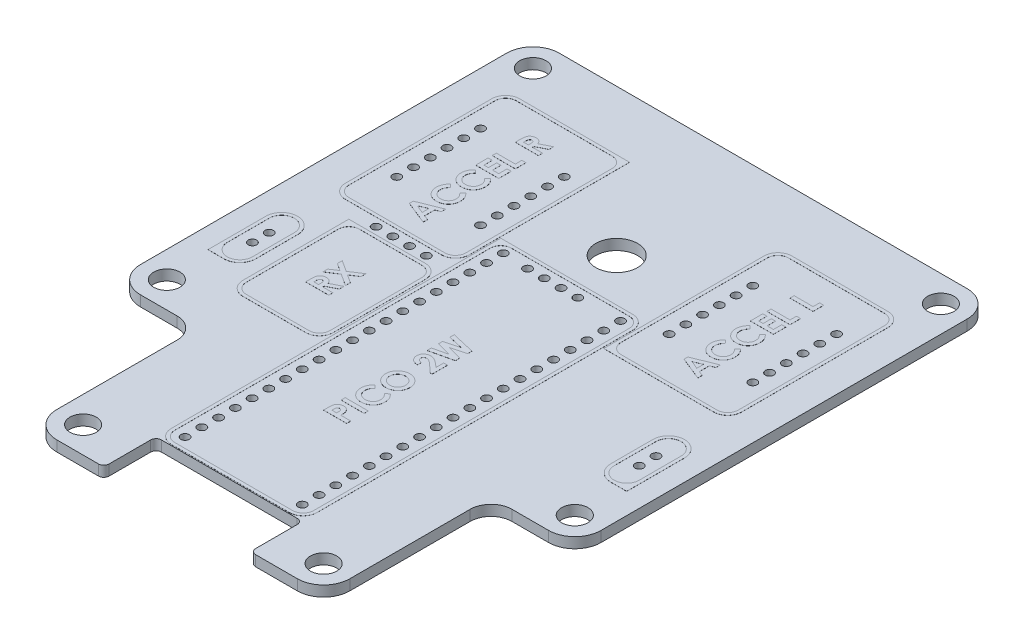
SolidWorks part; units mm, degrees
ref_plane "Front Plane" through (0, 0, 0) normal (0, 0, 1) x (1, 0, 0)
ref_plane "Top Plane" through (0, 0, 0) normal (0, 1, 0) x (1, 0, 0)
ref_plane "Right Plane" through (0, 0, 0) normal (1, 0, 0) x (0, 0, -1)
sketch "Sketch1" plane through (0, 0, 0) normal (0, 1, 0) x (1, 0, 0)
  line L0 (-22.225, -31.75) -> (-22.225, -57.15)
  line L1 (-34.925, -31.75) -> (-22.225, -31.75)
  line L2 (-34.925, -31.75) -> (-34.925, 31.75)
  line L3 (-34.925, 31.75) -> (34.925, 31.75)
  line L4 (34.925, -31.75) -> (34.925, 31.75)
  line L5 (-34.925, -31.75) -> (34.925, 31.75) construction
  line L6 (-34.925, 31.75) -> (34.925, -31.75) construction
  line L7 (-22.225, -57.15) -> (22.225, -57.15)
  line L8 (22.225, -57.15) -> (22.225, -31.75)
  line L9 (22.225, -31.75) -> (34.925, -31.75)
  point P0 (0, 0)
  point P9 (0, -57.15)
  dimension "D1" = 69.85
  dimension "D2" = 63.5
  dimension "D3" = 44.45
  dimension "D4" = 25.4
extrude "Boss-Extrude1" add sketch "Sketch1" along normal blind 1.6002
sketch "Sketch2" plane through (0, 1.6002, 0) normal (0, 1, 0) x (1, 0, 0)
  line L1 (-10.541, -48.5648) -> (10.541, -48.5648) construction
  line L2 (-10.541, -48.5648) -> (-10.541, 2.4892) construction
  line L3 (-10.541, 2.4892) -> (10.541, 2.4892) construction
  line L4 (10.541, -48.5648) -> (10.541, 2.4892) construction
  line L5 (-10.541, -48.5648) -> (10.541, 2.4892) construction
  line L6 (-10.541, 2.4892) -> (10.541, -48.5648) construction
  line L7 (-8.89, 1.2192) -> (8.89, 1.2192) construction
  circle A0 centre (-8.89, 1.2192) radius 0.635
  circle A1 centre (8.89, 1.2192) radius 0.635
  point P0 (0, -23.0378)
  point P7 (0, 1.2192)
  dimension "D5" = 1.27
  dimension "D1" = 21.082
  dimension "D2" = 51.054
  dimension "D3" = 23.0378
  dimension "D4" = 8.89
  dimension "D6" = 1.27
extrude "Cut-Extrude1" cut sketch "Sketch2" against normal blind 1.6002
pattern_linear "LPattern1" count 20 spacing 2.54 along (0, 0, 1) of "Cut-Extrude1"
sketch "Sketch3" plane through (0, 1.6002, 0) normal (0, 1, 0) x (1, 0, 0)
  line L0 (-27.0002, 15.875) -> (-14.3002, 15.875) construction
  line L1 (-29.5402, -3.175) -> (-11.7602, -3.175) construction
  line L2 (-29.5402, -3.175) -> (-29.5402, 22.225) construction
  line L3 (-29.5402, 22.225) -> (-11.7602, 22.225) construction
  line L4 (-11.7602, -3.175) -> (-11.7602, 22.225) construction
  line L5 (-29.5402, -3.175) -> (-11.7602, 22.225) construction
  line L6 (-29.5402, 22.225) -> (-11.7602, -3.175) construction
  line L7 (-20.6502, 15.875) -> (-20.6502, 9.525) construction
  line L9 (14.3002, 15.875) -> (27.0002, 15.875) construction
  line L10 (11.7602, -3.175) -> (29.5402, -3.175) construction
  line L11 (11.7602, -3.175) -> (11.7602, 22.225) construction
  line L12 (11.7602, 22.225) -> (29.5402, 22.225) construction
  line L13 (29.5402, -3.175) -> (29.5402, 22.225) construction
  line L14 (11.7602, -3.175) -> (29.5402, 22.225) construction
  line L15 (11.7602, 22.225) -> (29.5402, -3.175) construction
  line L16 (20.6502, 15.875) -> (20.6502, 9.525) construction
  line L17 (-11.7602, 22.225) -> (11.7602, 22.225) construction
  line L18 (0, 0) -> (0, 22.225) construction
  circle A0 centre (-14.3002, 15.875) radius 0.635
  circle A1 centre (-27.0002, 15.875) radius 0.635
  circle A2 centre (-8.89, 1.2192) radius 0.635 construction
  circle A3 centre (27.0002, 15.875) radius 0.635
  circle A4 centre (14.3002, 15.875) radius 0.635
  point P0 (-20.6502, 9.525)
  point P16 (20.6502, 9.525)
  dimension "D1" = 17.78
  dimension "D2" = 25.4
  dimension "D3" = 12.7
  dimension "D4" = 6.35
  dimension "D5" = 9.525
  dimension "D6" = 20.6502
  dimension "D7" = 17.78
  dimension "D8" = 25.4
extrude "Cut-Extrude2" cut sketch "Sketch3" against normal through all both and the other way through all
pattern_linear "LPattern2" count 6 spacing 2.54 along (0, 0, 1) of "Cut-Extrude2"
fillet "Fillet1" radius 3.9878 6 edges at (-34.925, 0.8001, -31.75) (34.925, 0.8001, -31.75) (-34.925, 0.8001, 31.75) (-22.225, 0.8001, 57.15) (22.225, 0.8001, 57.15) (34.925, 0.8001, 31.75)
sketch "Sketch9" plane through (0, 1.6002, 0) normal (0, 1, 0) x (1, 0, 0)
  line L1 (-30.9372, -27.7622) -> (30.9372, -27.7622) construction
  line L2 (-30.9372, -27.7622) -> (-30.9372, 27.7622) construction
  line L3 (-30.9372, 27.7622) -> (30.9372, 27.7622) construction
  line L4 (30.9372, -27.7622) -> (30.9372, 27.7622) construction
  line L5 (-30.9372, -27.7622) -> (30.9372, 27.7622) construction
  line L6 (-30.9372, 27.7622) -> (30.9372, -27.7622) construction
  circle A0 centre (-30.9372, 27.7622) radius 1.9939
  circle A1 centre (30.9372, 27.7622) radius 1.9939
  circle A2 centre (30.9372, -27.7622) radius 1.9939
  circle A3 centre (-30.9372, -27.7622) radius 1.9939
  arc A4 (-30.9372, 31.75) -> (-34.925, 27.7622) centre (-30.9372, 27.7622) ccw construction
  circle A5 centre (-18.2372, -53.1622) radius 1.9939
  circle A6 centre (18.2372, -53.1622) radius 1.9939
  point P0 (0, 0)
  dimension "D1" = 3.9878
extrude "Cut-Extrude4" cut sketch "Sketch9" against normal through all both and the other way through all
fillet "Fillet3" radius 3.175 2 edges at (22.225, 0.8001, 31.75) (-22.225, 0.8001, 31.75)
sketch "Sketch13" plane through (0, 1.6002, 0) normal (0, 1, 0) x (1, 0, 0)
  line L0 (-10.541, 0.889) -> (-10.541, -46.9646)
  line L1 (-8.9408, -48.5648) -> (8.9408, -48.5648)
  line L2 (10.541, -46.9646) -> (10.541, 0.889)
  line L3 (8.9408, 2.4892) -> (-8.9408, 2.4892)
  line L5 (-8.9408, -49.0728) -> (8.9408, -49.0728)
  line L6 (11.049, -46.9646) -> (11.049, 0.889)
  line L13 (-29.5402, 20.6248) -> (-29.5402, -1.5748)
  line L14 (-27.94, -3.175) -> (-13.3604, -3.175)
  line L15 (-11.7602, -1.5748) -> (-11.7602, 20.6248)
  line L16 (-13.3604, 22.225) -> (-27.94, 22.225)
  line L17 (11.7602, 20.6248) -> (11.7602, -1.5748)
  line L18 (13.3604, -3.175) -> (27.94, -3.175)
  line L19 (29.5402, -1.5748) -> (29.5402, 20.6248)
  line L20 (27.94, 22.225) -> (13.3604, 22.225)
  line L22 (-30.0482, 20.6248) -> (-30.0482, -1.5748)
  line L23 (-27.94, -3.683) -> (-13.3604, -3.683)
  line L25 (27.94, 22.733) -> (13.3604, 22.733)
  line L28 (30.0482, -1.5748) -> (30.0482, 20.6248)
  line L29 (-11.049, 0.889) -> (-11.049, -46.9646) construction
  line L30 (8.9408, 2.9972) -> (-8.9408, 2.9972) construction
  line L31 (8.9408, 2.9972) -> (-11.049, 2.9972)
  line L32 (-11.049, -46.9646) -> (-11.049, 2.9972)
  line L57 (-11.2522, -1.5748) -> (-11.2522, 20.6248) construction
  line L58 (-13.3604, 22.733) -> (-27.94, 22.733) construction
  line L59 (-27.94, 22.733) -> (-11.2522, 22.733)
  line L60 (-11.2522, 22.733) -> (-11.2522, -1.5748)
  line L61 (13.3604, -3.683) -> (27.94, -3.683) construction
  line L62 (11.2522, 20.6248) -> (11.2522, -1.5748) construction
  line L63 (11.2522, 20.6248) -> (11.2522, -3.683)
  line L64 (11.2522, -3.683) -> (27.94, -3.683)
  arc A0 (8.9408, 2.4892) -> (10.541, 0.889) centre (8.9408, 0.889) cw
  arc A1 (10.541, -46.9646) -> (8.9408, -48.5648) centre (8.9408, -46.9646) cw
  arc A2 (-8.9408, -48.5648) -> (-10.541, -46.9646) centre (-8.9408, -46.9646) cw
  arc A3 (-10.541, 0.889) -> (-8.9408, 2.4892) centre (-8.9408, 0.889) cw
  arc A4 (-8.9408, -49.0728) -> (-11.049, -46.9646) centre (-8.9408, -46.9646) cw
  arc A5 (11.049, -46.9646) -> (8.9408, -49.0728) centre (8.9408, -46.9646) cw
  arc A6 (8.9408, 2.9972) -> (11.049, 0.889) centre (8.9408, 0.889) cw
  arc A9 (11.7602, -1.5748) -> (13.3604, -3.175) centre (13.3604, -1.5748) ccw
  arc A10 (27.94, -3.175) -> (29.5402, -1.5748) centre (27.94, -1.5748) ccw
  arc A11 (29.5402, 20.6248) -> (27.94, 22.225) centre (27.94, 20.6248) ccw
  arc A12 (13.3604, 22.225) -> (11.7602, 20.6248) centre (13.3604, 20.6248) ccw
  arc A13 (-13.3604, 22.225) -> (-11.7602, 20.6248) centre (-13.3604, 20.6248) cw
  arc A14 (-11.7602, -1.5748) -> (-13.3604, -3.175) centre (-13.3604, -1.5748) cw
  arc A15 (-27.94, -3.175) -> (-29.5402, -1.5748) centre (-27.94, -1.5748) cw
  arc A16 (-29.5402, 20.6248) -> (-27.94, 22.225) centre (-27.94, 20.6248) cw
  arc A17 (-30.0482, 20.6248) -> (-27.94, 22.733) centre (-27.94, 20.6248) cw
  arc A18 (-27.94, -3.683) -> (-30.0482, -1.5748) centre (-27.94, -1.5748) cw
  arc A19 (-11.2522, -1.5748) -> (-13.3604, -3.683) centre (-13.3604, -1.5748) cw
  arc A21 (13.3604, 22.733) -> (11.2522, 20.6248) centre (13.3604, 20.6248) ccw
  arc A23 (27.94, -3.683) -> (30.0482, -1.5748) centre (27.94, -1.5748) ccw
  arc A24 (30.0482, 20.6248) -> (27.94, 22.733) centre (27.94, 20.6248) ccw
  arc A25 (-11.049, 0.889) -> (-8.9408, 2.9972) centre (-8.9408, 0.889) cw construction
  arc A43 (-13.3604, 22.733) -> (-11.2522, 20.6248) centre (-13.3604, 20.6248) cw construction
  arc A44 (11.2522, -1.5748) -> (13.3604, -3.683) centre (13.3604, -1.5748) ccw construction
  point P10 (10.541, 2.4892)
  point P13 (10.541, -48.5648)
  point P16 (-10.541, -48.5648)
  point P19 (-10.541, 2.4892)
  point P53 (11.7602, -3.175)
  point P56 (29.5402, -3.175)
  point P59 (29.5402, 22.225)
  point P62 (11.7602, 22.225)
  point P68 (-11.7602, -3.175)
  point P71 (-29.5402, -3.175)
  point P74 (-29.5402, 22.225)
  point P153 (26.5939, -10.8077)
  point P154 (0, 0)
  dimension "D1" = 1.6002
  dimension "D4" = 1.6002
  dimension "D13" = 0.508
  dimension "D2" = 0.508
  dimension "D5" = 0.508
extrude "Boss-Extrude5" add sketch "Sketch13" along normal blind 0.0127 contours A19 L60 L59 A17 L22 A18 L23 L13 A16 L16 A13 L15 A14 L14 A15 | L28 A24 L25 A21 L63 L64 A23 A12 L20 A11 L19 A10 L18 A9 L17 | A6 L31 L32 A4 L5 A5 L6 L0 A3 L3 A0 L2 A1 L1 A2 region at (-10.3915, 1.6002, 48.4153) region at (-29.2015, 1.6002, -21.8863) region at (29.2015, 1.6002, -21.8863)
sketch "Sketch15" plane through (0, 0, 0) normal (0, -1, 0) x (1, 0, 0)
  line L0 (-5.334, 1.3766) -> (2.8956, 1.3766)
  line L1 (-5.334, -2.9414) -> (2.8956, -2.9414)
  line L2 (-6.9342, -1.3412) -> (-6.9342, -0.7316)
  line L3 (-5.334, 0.8686) -> (2.8956, 0.8686)
  line L4 (4.4958, -1.3412) -> (4.4958, -0.7316)
  line L5 (-6.9342, -2.9414) -> (4.4958, 0.8686) construction
  line L6 (-6.9342, 0.8686) -> (4.4958, -2.9414) construction
  line L7 (5.0038, -1.3412) -> (5.0038, -0.7316)
  line L8 (-5.334, -3.4494) -> (2.8956, -3.4494)
  line L9 (-7.4422, -1.3412) -> (-7.4422, -0.7316)
  line L10 (2.8956, 1.3766) -> (5.0038, 1.3766)
  line L11 (5.0038, 1.3766) -> (5.0038, -0.7316)
  arc A0 (-5.334, 0.8686) -> (-6.9342, -0.7316) centre (-5.334, -0.7316) ccw
  arc A1 (-6.9342, -1.3412) -> (-5.334, -2.9414) centre (-5.334, -1.3412) ccw
  arc A2 (2.8956, -2.9414) -> (4.4958, -1.3412) centre (2.8956, -1.3412) ccw
  arc A3 (4.4958, -0.7316) -> (2.8956, 0.8686) centre (2.8956, -0.7316) ccw
  arc A4 (5.0038, -0.7316) -> (2.8956, 1.3766) centre (2.8956, -0.7316) ccw construction
  arc A5 (2.8956, -3.4494) -> (5.0038, -1.3412) centre (2.8956, -1.3412) ccw
  arc A6 (-7.4422, -1.3412) -> (-5.334, -3.4494) centre (-5.334, -1.3412) ccw
  arc A7 (-5.334, 1.3766) -> (-7.4422, -0.7316) centre (-5.334, -0.7316) ccw
  point P0 (-1.2192, -1.0364)
  point P32 (-1.2192, -2.9414)
  dimension "D1" = 1.6002
  dimension "D2" = 11.43
  dimension "D3" = 3.81
  dimension "D5" = 1.6002
  dimension "D6" = 1.2192
  dimension "D4" = 0.508
sketch "Sketch16" plane through (0, 1.6002, 0) normal (0, 1, 0) x (1, 0, 0)
  line L0 (-11.1125, -57.15) -> (-11.1125, -50.038)
  line L1 (-18.2372, -57.15) -> (18.2372, -57.15) construction
  line L2 (-10.2997, -49.2252) -> (10.2997, -49.2252)
  line L3 (11.1125, -50.038) -> (11.1125, -57.15)
  line L4 (11.1125, -57.15) -> (-11.1125, -57.15)
  arc A0 (11.1125, -50.038) -> (10.2997, -49.2252) centre (10.2997, -50.038) ccw
  arc A1 (-11.1125, -50.038) -> (-10.2997, -49.2252) centre (-10.2997, -50.038) cw
  point P8 (11.1125, -49.2252)
  point P11 (-11.1125, -49.2252)
  point P12 (0, -49.2252)
  point P13 (0, 0)
  dimension "D3" = 0.8128
  dimension "D1" = 22.225
  dimension "D2" = 7.9248
extrude "Cut-Extrude12" cut sketch "Sketch16" against normal through all both and the other way through all
fillet "Fillet4" radius 0.8128 2 edges at (11.1125, 0.8001, 57.15) (-11.1125, 0.8001, 57.15)
sketch "Sketch11" plane through (0, 1.6002, 0) normal (0, 1, 0) x (1, 0, 0)
  line L0 (0, 0) -> (0, 22.225) construction
  circle A0 centre (0, 9.525) radius 3.175
  dimension "D1" = 6.35
extrude "Cut-Extrude6" cut sketch "Sketch11" against normal through all both and the other way through all
sketch "Sketch18" plane through (0, 1.6002, 0) normal (0, 1, 0) x (1, 0, 0)
  line L0 (-22.0218, -4.9403) -> (-19.4818, -4.9403) construction
  line L1 (-24.5618, -6.5405) -> (-11.8618, -6.5405) construction
  line L2 (-24.5618, -6.5405) -> (-24.5618, -23.6855) construction
  line L3 (-24.5618, -23.6855) -> (-11.8618, -23.6855) construction
  line L4 (-11.8618, -6.5405) -> (-11.8618, -23.6855) construction
  line L5 (-19.4818, -4.9403) -> (-16.9418, -4.9403) construction
  line L6 (-16.9418, -4.9403) -> (-14.4018, -4.9403) construction
  line L7 (-22.0218, -4.9403) -> (-24.5618, -4.9403) construction
  line L8 (-14.4018, -4.9403) -> (-11.8618, -4.9403) construction
  circle A0 centre (-22.0218, -4.9403) radius 0.635
  circle A1 centre (-19.4818, -4.9403) radius 0.635
  circle A2 centre (-16.9418, -4.9403) radius 0.635
  circle A3 centre (-14.4018, -4.9403) radius 0.635
  circle A4 centre (-27.0002, 3.175) radius 0.635 construction
  point P14 (-11.8618, -15.113)
  point P17 (-19.3548, -2.1209)
  point P20 (-18.2118, -6.5405)
  dimension "D1" = 12.7
  dimension "D2" = 17.145
  dimension "D3" = 2.54
  dimension "D4" = 18.2118
  dimension "D5" = 15.113
  dimension "D6" = 1.6002
extrude "Cut-Extrude13" cut sketch "Sketch18" against normal through all both and the other way through all
sketch "Sketch20" plane through (0, 1.6002, 0) normal (0, 1, 0) x (1, 0, 0)
  line L0 (-24.5618, -6.5405) -> (-11.8618, -6.5405) construction
  line L1 (-22.9616, -6.5405) -> (-13.462, -6.5405)
  line L2 (-24.5618, -8.1407) -> (-24.5618, -22.0853)
  line L3 (-22.9616, -23.6855) -> (-13.462, -23.6855)
  line L4 (-11.8618, -8.1407) -> (-11.8618, -22.0853)
  line L5 (-11.8618, -6.5405) -> (-11.8618, -23.6855) construction
  line L6 (-24.5618, -23.6855) -> (-11.8618, -23.6855) construction
  line L7 (-24.5618, -6.5405) -> (-24.5618, -23.6855) construction
  line L8 (-22.9616, -6.0325) -> (-13.462, -6.0325)
  line L9 (-11.3538, -8.1407) -> (-11.3538, -22.0853)
  line L10 (-22.9616, -24.1935) -> (-13.462, -24.1935)
  line L11 (-25.0698, -8.1407) -> (-25.0698, -22.0853)
  line L12 (-25.0698, -8.1407) -> (-25.0698, -6.0325)
  line L13 (-25.0698, -6.0325) -> (-22.9616, -6.0325)
  arc A0 (-13.462, -6.5405) -> (-11.8618, -8.1407) centre (-13.462, -8.1407) cw
  arc A1 (-11.8618, -22.0853) -> (-13.462, -23.6855) centre (-13.462, -22.0853) cw
  arc A2 (-22.9616, -23.6855) -> (-24.5618, -22.0853) centre (-22.9616, -22.0853) cw
  arc A3 (-24.5618, -8.1407) -> (-22.9616, -6.5405) centre (-22.9616, -8.1407) cw
  arc A4 (-13.462, -6.0325) -> (-11.3538, -8.1407) centre (-13.462, -8.1407) cw
  arc A5 (-11.3538, -22.0853) -> (-13.462, -24.1935) centre (-13.462, -22.0853) cw
  arc A6 (-22.9616, -24.1935) -> (-25.0698, -22.0853) centre (-22.9616, -22.0853) cw
  arc A8 (-25.0698, -8.1407) -> (-22.9616, -6.0325) centre (-22.9616, -8.1407) cw construction
  dimension "D1" = 1.6002
  dimension "D2" = 0.508
extrude "Boss-Extrude6" add sketch "Sketch20" along normal blind 0.0127
sketch "Sketch6" plane through (0, 1.6002, 0) normal (0, 1, 0) x (1, 0, 0)
  line L0 (1.6002, -48.5648) -> (1.6002, 2.4892) construction
  line L1 (-20.6502, -3.175) -> (-19.05, -3.175) construction
  line L2 (-10.541, 2.4892) -> (10.541, 2.4892) construction
  line L3 (1.6002, -23.0378) -> (0.8636, -23.0378) construction
  line L4 (-19.05, -3.175) -> (-19.05, 22.225) construction
  line L5 (22.2504, -3.175) -> (22.2504, 22.225) construction
  line L6 (-10.541, -48.5648) -> (10.541, -48.5648) construction
  line L7 (-29.5402, 22.225) -> (-11.7602, 22.225) construction
  line L8 (-29.5402, -3.175) -> (-11.7602, -3.175) construction
  line L9 (11.7602, -3.175) -> (29.5402, -3.175) construction
  line L10 (22.2504, -3.175) -> (20.6502, -3.175) construction
  line L11 (-16.6116, -6.5405) -> (-16.6116, -23.6855) construction
  line L12 (-13.462, -6.5405) -> (-22.9616, -6.5405) construction
  line L13 (-22.9616, -23.6855) -> (-13.462, -23.6855) construction
  line L14 (-13.462, -6.5405) -> (-22.9616, -6.5405) construction
  text T0 "<b>PICO 2W</b>"
  text T1 "<b>ACCEL R</b>"
  text T2 "<b>ACCEL L</b>"
  text T3 "<b>RX</b>"
  point P12 (20.6502, -3.175)
  point P24 (-18.2118, -6.5405)
  point P34 (-20.6502, -3.175)
  dimension "D1" = 1.6002
  dimension "D2" = 1.6002
  dimension "D3" = 1.6002
sketch "Sketch21" plane through (0, 1.6002, 0) normal (0, 1, 0) x (1, 0, 0)
  line L0 (-29.337, -13.843) -> (-29.337, -16.383) construction
  line L1 (-34.925, 27.7622) -> (-34.925, -27.7622) construction
  line L2 (-29.337, -15.113) -> (-24.5618, -15.113) construction
  line L3 (-24.5618, -6.5405) -> (-24.5618, -23.6855) construction
  circle A0 centre (-29.337, -13.843) radius 0.635
  circle A1 centre (-29.337, -16.383) radius 0.635
  circle A2 centre (-22.0218, -4.9403) radius 0.635 construction
  dimension "D1" = 2.54
  dimension "D2" = 5.588
extrude "Cut-Extrude14" cut sketch "Sketch21" against normal through all both and the other way through all
sketch "Sketch22" plane through (0, 1.6002, 0) normal (0, 1, 0) x (1, 0, 0)
  line L0 (-29.337, -13.843) -> (-29.337, -16.383) construction
  line L1 (-31.242, -11.938) -> (-27.432, -11.938) construction
  line L2 (-31.242, -11.938) -> (-31.242, -18.288)
  line L3 (-31.242, -18.288) -> (-27.432, -18.288) construction
  line L4 (-27.432, -11.938) -> (-27.432, -18.288)
  line L5 (-29.337, -15.113) -> (-27.432, -15.113) construction
  line L6 (-29.337, -15.113) -> (-31.242, -15.113) construction
  line L19 (-31.75, -11.938) -> (-31.75, -18.288)
  line L20 (-26.924, -11.938) -> (-26.924, -18.288)
  line L21 (-29.337, -20.701) -> (-31.75, -20.701)
  line L22 (-31.75, -20.701) -> (-31.75, -18.288)
  arc A0 (-27.432, -11.938) -> (-31.242, -11.938) centre (-29.337, -11.938) ccw
  arc A1 (-27.432, -18.288) -> (-31.242, -18.288) centre (-29.337, -18.288) cw
  arc A14 (-26.924, -11.938) -> (-31.75, -11.938) centre (-29.337, -11.938) ccw
  arc A15 (-26.924, -18.288) -> (-29.337, -20.701) centre (-29.337, -18.288) cw
  arc A17 (-26.924, -18.288) -> (-31.75, -18.288) centre (-29.337, -18.288) cw construction
  dimension "D1" = 3.81
  dimension "D2" = 6.35
  dimension "D3" = 0.508
extrude "Boss-Extrude7" add sketch "Sketch22" along normal up to surface (0.0127 mm away) up to face at (-17.4709, 1.6129, 16.1714)
mirror "Mirror1" about plane through (0, 0, 0) normal (1, 0, 0) of "Boss-Extrude7", "Cut-Extrude14"
extrude "Boss-Extrude8" add sketch "Sketch6" along normal blind 0.0127
extrude "Boss-Extrude9" add sketch "Sketch15" along normal blind 0.0127
sketch "Sketch23" plane through (0, 0, 0) normal (0, -1, 0) x (1, 0, 0)
  line L0 (-2.4892, -1.0364) -> (0.0508, -1.0364) construction
  line L1 (0.0508, -1.0364) -> (2.5908, -1.0364) construction
  line L2 (-2.4892, -1.0364) -> (-5.0292, -1.0364) construction
  circle A0 centre (-2.4892, -1.0364) radius 0.635
  circle A1 centre (-5.0292, -1.0364) radius 0.635
  circle A2 centre (0.0508, -1.0364) radius 0.635
  circle A3 centre (2.5908, -1.0364) radius 0.635
  point P8 (-1.2192, -1.0364)
  point P9 (0, 0)
  dimension "D1" = 1.27
  dimension "D2" = 2.54
extrude "Cut-Extrude15" cut sketch "Sketch23" against normal through all both and the other way through all
